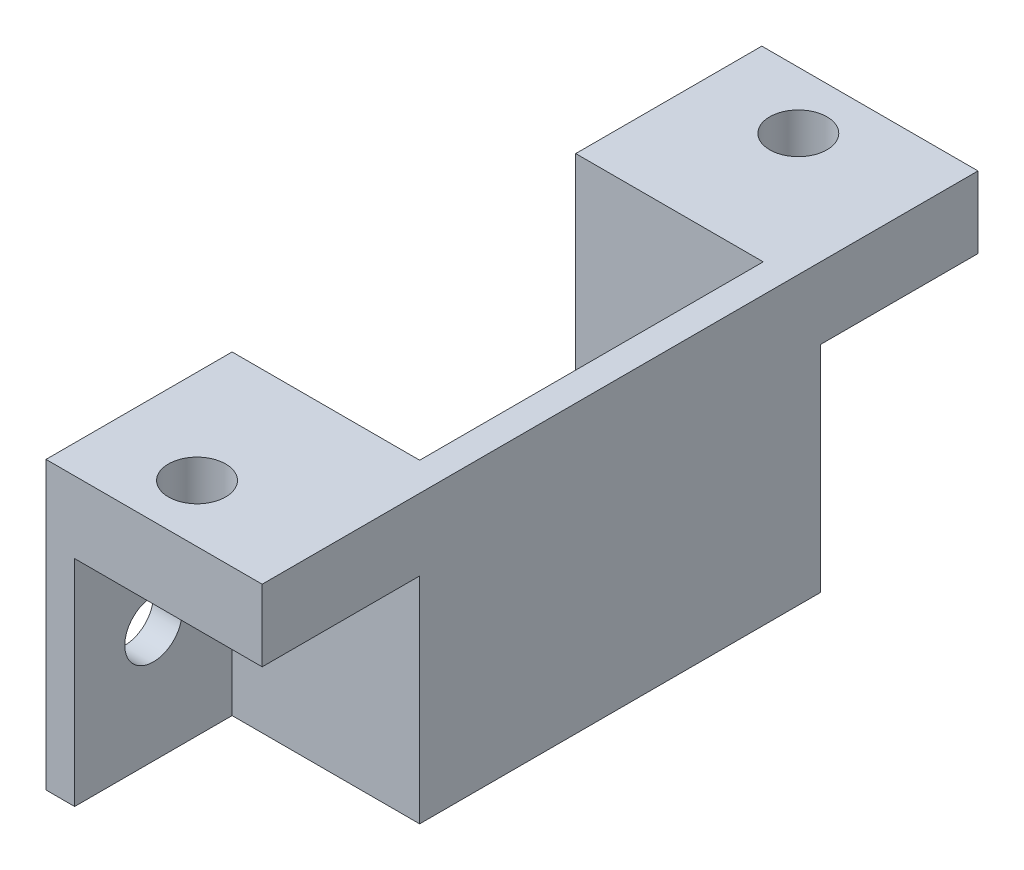
SolidWorks part; units mm, degrees
ref_plane "Płaszczyzna przednia" through (0, 0, 0) normal (0, 0, 1) x (1, 0, 0)
ref_plane "Płaszczyzna górna" through (0, 0, 0) normal (0, 1, 0) x (1, 0, 0)
ref_plane "Płaszczyzna prawa" through (0, 0, 0) normal (1, 0, 0) x (0, 0, -1)
sketch "Sketch1" plane through (0, 0, 0) normal (0, 1, 0) x (1, 0, 0)
  line L1 (15.1, 14) -> (15.1, 25)
  line L3 (0, 14) -> (2, 14)
  line L4 (0, 14) -> (0, 25)
  line L5 (0, 25) -> (2, 25)
  line L6 (0, 14) -> (15.1, 14)
  line L7 (0, 12) -> (13.1, 12)
  line L8 (0, 12) -> (0, -12)
  line L9 (0, -12) -> (13.1, -12)
  line L10 (13.1, 12) -> (13.1, -12)
  line L11 (15.1, 14) -> (15.1, -14)
  line L12 (0, -14) -> (15.1, -14)
  line L13 (0, 14) -> (0, -14)
  line L14 (2, 14) -> (2, 25)
  line L15 (0, -14) -> (2, -14)
  line L16 (0, -14) -> (0, -25)
  line L17 (0, -25) -> (2, -25)
  line L18 (2, -14) -> (2, -25)
  line L19 (15.1, 25) -> (2, 25)
  line L20 (6.55, 29.9244) -> (6.55, -34.5201) construction
  line L21 (15.1, -14) -> (15.1, -25)
  line L22 (15.1, -25) -> (2, -25)
  line L23 (-22.5276, 0) -> (51.0243, 0) construction
  circle A0 centre (6.55, 21) radius 2
  circle A1 centre (6.55, -21) radius 2
  point P7 (0, 0)
  point P32 (6.55, 12)
  dimension "D1" = 4
  dimension "D2" = 9
  dimension "D8" = 2
  dimension "D9" = 2
  dimension "D3" = 4
  dimension "D5" = 13.1
  dimension "D6" = 24
  dimension "D7" = 2
  dimension "D4" = 9
  dimension "D10" = 50
extrude "Boss-Extrude1" add sketch "Sketch1" along normal blind 20 contours L3 L13 L7 L10 L9 L12 L11 L6 | L3 L14 L5 L4 | L18 L12 L16 L17 region at (14.7819, 0, 0) region at (1, 0, -19.5) region at (1, 0, 19.5)
sketch "Sketch4" plane through (2, 0, 0) normal (1, 0, 0) x (0, 0, -1)
  line L0 (-19.5, 20) -> (-19.5, 0) construction
  line L1 (-14, 20) -> (-25, 20) construction
  line L2 (-14, 0) -> (-25, 0) construction
  line L3 (14, 20) -> (25, 20) construction
  circle A0 centre (-19.5, 8) radius 2
  circle A1 centre (19.5, 8) radius 2
  point P15 (19.5, 20)
  dimension "D1" = 4
  dimension "D2" = 4
  dimension "D3" = 8
extrude "Cut-Extrude1" cut sketch "Sketch4" along normal through all both and the other way through all
extrude "Boss-Extrude2" add sketch "Sketch1<31>" against normal blind 5 from surface contours A1 L20 L22 L21 L12 | L20 A1 L12 L18 L22 | L19 L20 A0 L6 L1 | L20 L19 L14 L6 A0 region at (8.7411, 0, -19.3567) region at (8.7411, 0, 19.3567) starting at face at (5.3667, 20, 0)
sketch "Sketch1<31>" plane through (0, 0, 0) normal (0, 1, 0) x (1, 0, 0) same geometry as "Sketch1"
